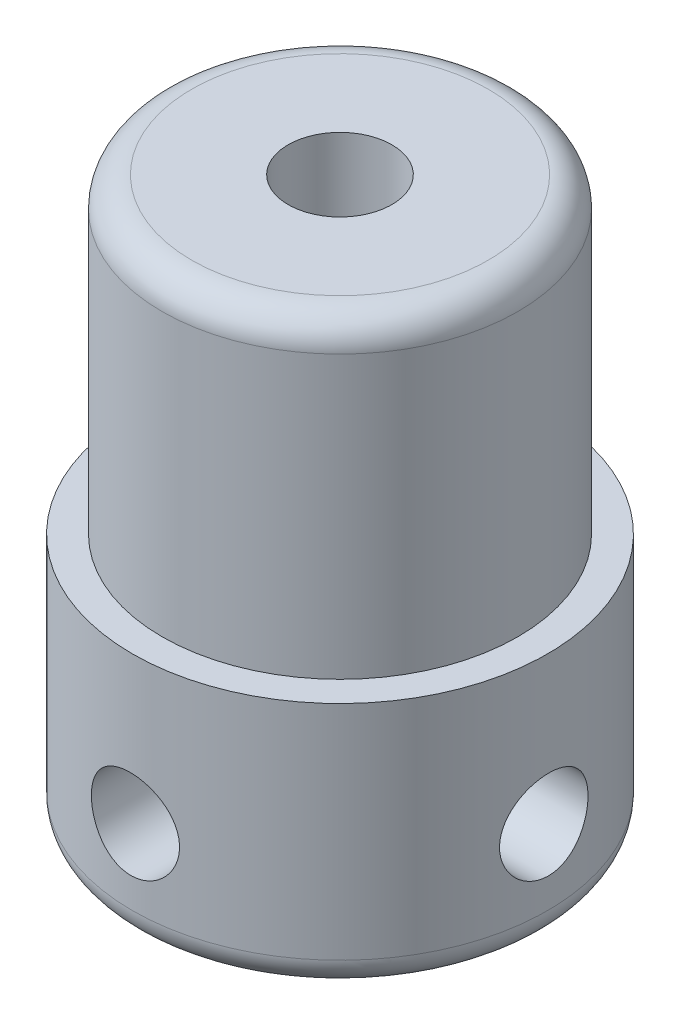
SolidWorks part; units mm, degrees
ref_plane "前视基准面" through (0, 0, 0) normal (0, 0, 1) x (1, 0, 0)
ref_plane "上视基准面" through (0, 0, 0) normal (0, 1, 0) x (1, 0, 0)
ref_plane "右视基准面" through (0, 0, 0) normal (1, 0, 0) x (0, 0, -1)
sketch "草图1" plane through (0, 0, 0) normal (0, 1, 0) x (1, 0, 0)
  circle A0 centre (-14.3124, 6.4073) radius 7
  circle A1 centre (-14.3124, 6.4073) radius 3
extrude "凸台-拉伸1" add sketch "草图1" along normal blind 8.5
sketch "草图2" plane through (0, 8.5, 0) normal (0, 1, 0) x (1, 0, 0)
  circle A0 centre (-14.3124, 6.4073) radius 6
  circle A1 centre (-14.3124, 6.4073) radius 1.75
extrude "凸台-拉伸2" add sketch "草图2" along normal blind 10.5
fillet "圆角1" radius 1 2 edges at (-14.3124, 0, 0.5927) (-14.3124, 19, -0.4073)
sketch "草图3" plane through (0, 0, 0) normal (1, 0, 0) x (0, 0, -1)
  line L0 (0.4073, 0) -> (12.4073, 0) construction
  circle A0 centre (6.4428, 3.5) radius 1.5
  dimension "D1" = 3.5
extrude "切除-拉伸1" cut sketch "草图3" against normal blind 14.5
sketch "草图4" plane through (0, 0, 0) normal (0, 0, 1) x (1, 0, 0)
  line L0 (-20.3124, 0) -> (-8.3124, 0) construction
  circle A0 centre (-14.3741, 3.5) radius 1.5
  dimension "D1" = 3.5
extrude "切除-拉伸2" cut sketch "草图4" against normal blind 6.5 and the other way blind 6.5
equation "\"8.5、\"=10"
